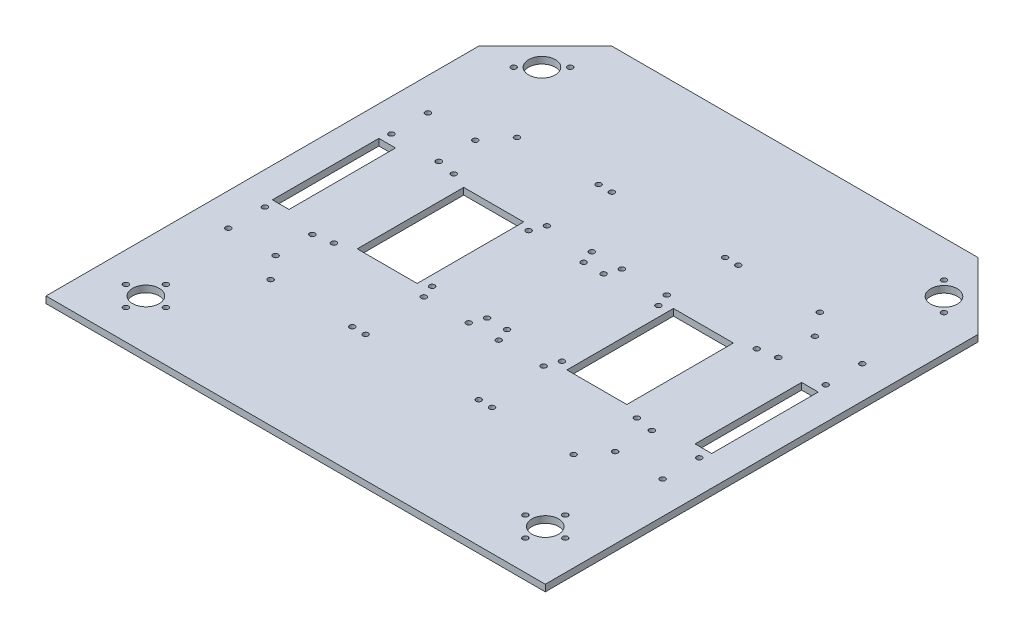
SolidWorks part; units mm, degrees
ref_plane "Plan de face" through (0, 0, 0) normal (0, 0, 1) x (1, 0, 0)
ref_plane "Plan de dessus" through (0, 0, 0) normal (0, 1, 0) x (1, 0, 0)
ref_plane "Plan de droite" through (0, 0, 0) normal (1, 0, 0) x (0, 0, -1)
sketch "Esquisse1" plane through (0, 0, 0) normal (0, 1, 0) x (1, 0, 0)
  line L0 (-150, 0) -> (-150, 260)
  line L2 (150, 0) -> (150, 260)
  line L3 (-150, 260) -> (-110, 260) construction
  line L4 (-110, 260) -> (-110, 300) construction
  line L5 (150, 260) -> (110, 260) construction
  line L6 (110, 260) -> (110, 300) construction
  line L8 (-150, 260) -> (-110, 300)
  line L9 (-110, 300) -> (110, 300)
  line L10 (0, 0) -> (0, 300) construction
  line L11 (110, 300) -> (150, 260)
  line L12 (-150, 0) -> (-119.9849, 0) construction
  line L13 (-119.9849, 0) -> (-119.9849, 30) construction
  line L14 (150, 0) -> (120, 0) construction
  line L15 (120, 0) -> (120, 30) construction
  line L16 (-150, 0) -> (150, 0)
  line L17 (-150, 260) -> (-120, 260) construction
  line L18 (-120, 260) -> (-120, 268) construction
  line L19 (150, 260) -> (120, 260) construction
  line L20 (120, 260) -> (120, 269.5596) construction
  line L21 (-120, 268) -> (-111.5147, 276.4853) construction
  line L22 (-120, 268) -> (-128.4853, 259.5147) construction
  line L23 (120, 269.5596) -> (128.4853, 261.0743) construction
  line L24 (120, 269.5596) -> (111.5147, 278.0449) construction
  line L25 (120, 0) -> (120, 19.3937) construction
  line L26 (120, 30) -> (120, 19.3937) construction
  line L27 (120, 30) -> (120, 42) construction
  line L28 (-119.9849, 0) -> (-119.9849, 18) construction
  line L29 (-119.9849, 18) -> (-119.9849, 30) construction
  line L30 (-119.9849, 30) -> (-119.9849, 42) construction
  line L31 (120, 0) -> (120, 18) construction
  line L32 (150, 150) -> (-150, 150) construction
  line L33 (-119.9849, 30) -> (-107.9849, 30) construction
  line L34 (-119.9849, 30) -> (-131.9849, 30) construction
  line L35 (120, 30) -> (132, 30) construction
  line L36 (120, 30) -> (108, 30) construction
  circle A2 centre (-119.9849, 30) radius 8
  circle A4 centre (-120, 268) radius 8
  circle A5 centre (120, 269.5596) radius 8
  circle A6 centre (-111.5147, 276.4853) radius 1.6
  circle A7 centre (-128.4853, 259.5147) radius 1.6
  circle A8 centre (111.5147, 278.0449) radius 1.6
  circle A9 centre (128.4853, 261.0743) radius 1.6
  circle A10 centre (120, 30) radius 8
  circle A11 centre (120, 42) radius 1.6
  circle A13 centre (-119.9849, 42) radius 1.6
  circle A14 centre (-119.9849, 18) radius 1.6
  circle A15 centre (120, 18) radius 1.6
  circle A16 centre (-131.9849, 30) radius 1.6
  circle A17 centre (-107.9849, 30) radius 1.6
  circle A18 centre (108, 30) radius 1.6
  circle A19 centre (132, 30) radius 1.6
extrude "Boss.-Extru.1" add sketch "Esquisse1" along normal blind 4
sketch "Esquisse3" plane through (0, 4, 0) normal (0, 1, 0) x (1, 0, 0)
  line L0 (-150, 0) -> (150, 0) construction
  line L1 (150, 0) -> (150, 260) construction
  line L2 (150, 260) -> (110, 300) construction
  line L3 (110, 300) -> (-110, 300) construction
  line L4 (-110, 300) -> (-150, 260) construction
  line L5 (-150, 260) -> (-150, 0) construction
  line L6 (-150, 150) -> (150, 150) construction
  line L7 (0, 300) -> (0, 0) construction
  line L8 (0, 150) -> (-5, 150) construction
  line L9 (0, 150) -> (5, 150) construction
  line L10 (-5, 150) -> (-5, 175) construction
  line L11 (-5, 150) -> (-5, 109) construction
  line L12 (-5, 109) -> (-13, 109) construction
  line L13 (-13, 109) -> (-13, 117) construction
  line L14 (-13, 117) -> (-5, 117) construction
  line L15 (-5, 117) -> (-5, 109) construction
  line L16 (-13, 117) -> (-5, 109) construction
  line L17 (-13, 109) -> (-5, 117) construction
  line L18 (-5, 175) -> (-10, 175) construction
  line L19 (-10, 175) -> (-10, 183) construction
  line L20 (-10, 183) -> (-2, 183) construction
  line L23 (-5, 175) -> (-2, 175) construction
  line L24 (-2, 175) -> (-2, 183) construction
  line L25 (-10, 183) -> (-2, 175) construction
  line L26 (-10, 175) -> (-2, 183) construction
  line L27 (-5, 117) -> (-40, 117) construction
  line L28 (-40, 117) -> (-40, 175) construction
  line L29 (-40, 175) -> (-35, 175) construction
  line L30 (-35, 175) -> (-35, 125) construction
  line L31 (-35, 125) -> (-10, 125) construction
  line L32 (-10, 175) -> (-10, 125) construction
  line L33 (-40, 117) -> (-40, 109) construction
  line L34 (-40, 109) -> (-32, 109) construction
  line L35 (-32, 109) -> (-32, 117) construction
  line L36 (-32, 117) -> (-40, 109) construction
  line L37 (-40, 117) -> (-32, 109) construction
  line L38 (-40, 175) -> (-43, 175) construction
  line L39 (-43, 175) -> (-43, 183) construction
  line L40 (-43, 183) -> (-35, 183) construction
  line L41 (-35, 183) -> (-35, 175) construction
  line L42 (-35, 175) -> (-43, 183) construction
  line L43 (-43, 175) -> (-35, 183) construction
  line L44 (5, 125) -> (5, 183) construction
  line L45 (5, 125) -> (10, 125) construction
  line L47 (10, 125) -> (10, 175) construction
  line L50 (5, 183) -> (40, 183) construction
  line L51 (40, 183) -> (40, 125) construction
  line L52 (40, 125) -> (35, 125) construction
  line L53 (35, 125) -> (35, 175) construction
  line L54 (35, 175) -> (10, 175) construction
  line L55 (10, 125) -> (10, 117) construction
  line L56 (10, 117) -> (2, 117) construction
  line L57 (2, 117) -> (2, 125) construction
  line L58 (2, 125) -> (5, 125) construction
  line L59 (35, 125) -> (35, 117) construction
  line L60 (35, 117) -> (43, 117) construction
  line L61 (43, 117) -> (43, 125) construction
  line L62 (43, 125) -> (40, 125) construction
  line L63 (5, 183) -> (5, 191) construction
  line L64 (5, 191) -> (13, 191) construction
  line L65 (13, 191) -> (13, 183) construction
  line L66 (40, 183) -> (40, 191) construction
  line L67 (40, 191) -> (32, 191) construction
  line L68 (32, 191) -> (32, 183) construction
  line L69 (32, 183) -> (40, 191) construction
  line L70 (40, 183) -> (32, 191) construction
  line L71 (5, 191) -> (13, 183) construction
  line L72 (13, 191) -> (5, 183) construction
  line L73 (2, 125) -> (10, 117) construction
  line L74 (2, 117) -> (10, 125) construction
  line L75 (35, 125) -> (43, 117) construction
  line L76 (35, 117) -> (43, 125) construction
  circle A0 centre (-9, 113) radius 1.6
  circle A1 centre (-6, 179) radius 1.6
  circle A2 centre (-39, 179) radius 1.6
  circle A3 centre (-36, 113) radius 1.6
  circle A4 centre (9, 187) radius 1.6
  circle A5 centre (36, 187) radius 1.6
  circle A6 centre (39, 121) radius 1.6
  circle A7 centre (6, 121) radius 1.6
  dimension "D1" = 58
  dimension "D7" = 5
  dimension "D2" = 8
  dimension "D3" = 8
  dimension "D4" = 25
  dimension "D5" = 35
  dimension "D6" = 50
extrude "Enlèv. mat.-Extru.1" cut sketch "Esquisse3" against normal blind 10
sketch "Esquisse4" plane through (0, 4, 0) normal (0, 1, 0) x (1, 0, 0)
  line L0 (0, 150) -> (-45, 150)
  line L1 (0, 0) -> (0, 300) construction
  line L2 (150, 150) -> (-150, 150) construction
  line L3 (-45, 150) -> (-45, 182)
  line L4 (-45, 182) -> (-81, 182)
  line L5 (-81, 182) -> (-81, 118)
  line L6 (-81, 118) -> (-45, 118)
  line L7 (-45, 118) -> (-45, 150)
  line L8 (0, 150) -> (45, 150)
  line L9 (45, 150) -> (45, 182)
  line L10 (45, 182) -> (81, 182)
  line L11 (81, 182) -> (81, 118)
  line L12 (81, 118) -> (45, 118)
  line L13 (45, 118) -> (45, 150)
  dimension "D2" = 64
  dimension "D3" = 36
extrude "Enlèv. mat.-Extru.2" cut sketch "Esquisse4" against normal blind 5 contours L6 L7 L3 L4 L5 | L9 L10 L11 L12 L13 region at (-63, 4, -150)
mirror "Symétrie1" about plane through (0, 0, 0) normal (1, 0, 0) of "Enlèv. mat.-Extru.1"
sketch "Esquisse5" plane through (0, 4, 0) normal (0, 1, 0) x (1, 0, 0)
  line L0 (-150, 260) -> (-110, 300) construction
  line L1 (-110, 300) -> (110, 300) construction
  line L2 (110, 300) -> (150, 260) construction
  line L3 (150, 260) -> (150, 0) construction
  line L4 (150, 0) -> (-150, 0) construction
  line L5 (-150, 0) -> (-150, 260) construction
  line L6 (0, 150) -> (0, 205) construction
  line L7 (0, 0) -> (0, 300) construction
  line L8 (0, 150) -> (0, 95) construction
  line L9 (0, 205) -> (-5, 205) construction
  line L10 (0, 205) -> (-15, 205) construction
  line L11 (-10, 205) -> (-5, 205) construction
  line L13 (-15, 205) -> (-15, 195) construction
  line L14 (-15, 195) -> (-25, 195) construction
  line L16 (-25, 195) -> (-25, 215) construction
  line L17 (-25, 215) -> (-15, 215) construction
  line L18 (-15, 215) -> (-15, 205) construction
  line L19 (-25, 205) -> (-25, 210) construction
  line L20 (-25, 210) -> (-30, 210) construction
  line L21 (-30, 210) -> (-30, 200) construction
  line L22 (-30, 200) -> (-25, 200) construction
  line L23 (0, 205) -> (-30, 205)
  line L24 (-30, 205) -> (-30, 190) construction
  line L29 (-30, 220) -> (-30, 205) construction
  line L30 (-30, 220) -> (-30, 228) construction
  line L31 (-30, 228) -> (-38, 228) construction
  line L32 (-38, 228) -> (-38, 220) construction
  line L33 (-38, 220) -> (-30, 220) construction
  line L34 (-38, 228) -> (-46, 228) construction
  line L35 (-46, 228) -> (-46, 220) construction
  line L37 (-30, 220) -> (-95, 220) construction
  line L38 (-95, 220) -> (-95, 190) construction
  line L39 (-95, 190) -> (-30, 190) construction
  line L40 (95, 80) -> (95, 72) construction
  line L41 (95, 72) -> (87, 72) construction
  line L42 (-46, 228) -> (-38, 220) construction
  line L43 (-38, 220) -> (-30, 228) construction
  line L44 (-46, 220) -> (-38, 228) construction
  line L45 (-38, 228) -> (-30, 220) construction
  line L49 (87, 72) -> (87, 80) construction
  line L50 (87, 80) -> (95, 72) construction
  line L51 (0, 95) -> (30, 95) construction
  line L52 (30, 95) -> (30, 110) construction
  line L56 (30, 80) -> (30, 95) construction
  line L57 (30, 80) -> (30, 72) construction
  line L58 (30, 72) -> (38, 72) construction
  line L59 (38, 72) -> (38, 80) construction
  line L60 (38, 80) -> (30, 80) construction
  line L61 (38, 80) -> (46, 80) construction
  line L62 (46, 80) -> (46, 72) construction
  line L63 (46, 72) -> (38, 72) construction
  line L64 (46, 80) -> (38, 72) construction
  line L65 (30, 80) -> (38, 72) construction
  line L66 (30, 72) -> (38, 80) construction
  line L67 (46, 72) -> (38, 80) construction
  line L72 (30, 110) -> (95, 110) construction
  line L73 (95, 110) -> (95, 80) construction
  line L74 (95, 80) -> (46, 80) construction
  line L78 (95, 72) -> (87, 72) construction
  line L79 (87, 72) -> (95, 80) construction
  line L80 (95, 110) -> (95, 118) construction
  line L81 (95, 88) -> (95, 110) construction
  line L82 (95, 118) -> (87, 118) construction
  line L83 (87, 118) -> (87, 110) construction
  line L84 (87, 110) -> (95, 118) construction
  line L85 (95, 118) -> (87, 118) construction
  line L86 (87, 118) -> (95, 110) construction
  line L87 (-95, 190) -> (-95, 182) construction
  line L88 (95, 110) -> (95, 88) construction
  line L89 (-95, 182) -> (-87, 182) construction
  line L90 (-87, 182) -> (-87, 190) construction
  line L91 (-87, 190) -> (-95, 182) construction
  line L92 (-95, 182) -> (-87, 182) construction
  line L93 (-87, 182) -> (-95, 190) construction
  line L94 (-95, 190) -> (-95, 220) construction
  line L95 (-95, 220) -> (-95, 228) construction
  line L96 (-95, 228) -> (-87, 228) construction
  line L97 (-87, 228) -> (-87, 220) construction
  line L98 (-87, 220) -> (-95, 228) construction
  line L99 (-95, 228) -> (-95, 220) construction
  line L100 (-95, 220) -> (-87, 228) construction
  circle A2 centre (-42, 224) radius 1.6
  circle A3 centre (-34, 224) radius 1.6
  circle A4 centre (34, 76) radius 1.6
  circle A5 centre (42, 76) radius 1.6
  circle A13 centre (91, 114) radius 1.6
  circle A14 centre (91, 76) radius 1.6
  circle A15 centre (-91, 224) radius 1.6
  circle A16 centre (-91, 186) radius 1.6
  dimension "D1" = 30
  dimension "D2" = 55
extrude "Enlèv. mat.-Extru.4" cut sketch "Esquisse5" against normal blind 5 contours A3 | A2 | A13 | A14 | A4 | A5 | A16 | A15 region at (-42, 4, -224) region at (-34, 4, -224) region at (34, 4, -76) region at (42, 4, -76) region at (91, 4, -114) region at (91, 4, -76) region at (-91, 4, -224) region at (-91, 4, -186)
mirror "Symétrie4" about plane through (0, 0, 0) normal (1, 0, 0) of "Enlèv. mat.-Extru.4"
sketch "Esquisse6" plane through (0, 4, 0) normal (0, 1, 0) x (1, 0, 0)
  line L0 (-106, 150) -> (-106, 116) construction
  line L1 (-106, 116) -> (-98, 116) construction
  line L2 (0, 150) -> (-85, 150) construction
  line L3 (-85, 150) -> (-106, 150) construction
  line L4 (-98, 116) -> (-98, 108) construction
  line L5 (-98, 108) -> (-106, 108) construction
  line L6 (-106, 108) -> (-106, 116) construction
  line L8 (-106, 116) -> (-126.5, 116) construction
  line L11 (-106, 116) -> (-106, 86) construction
  line L12 (-126.5, 116) -> (-126.5, 86) construction
  line L13 (-126.5, 86) -> (-106, 86) construction
  line L14 (-106, 86) -> (-98, 86) construction
  line L15 (-98, 86) -> (-98, 94) construction
  line L16 (-98, 94) -> (-106, 94) construction
  line L17 (-106, 94) -> (-98, 86) construction
  line L18 (-106, 116) -> (-98, 108) construction
  line L19 (-106, 116) -> (-106, 108) construction
  line L20 (-106, 108) -> (-98, 116) construction
  line L21 (-126.5, 86) -> (-134.5, 86) construction
  line L22 (-134.5, 86) -> (-134.5, 94) construction
  line L23 (-134.5, 94) -> (-126.5, 94) construction
  line L24 (-126.5, 94) -> (-134.5, 86) construction
  line L25 (-134.5, 86) -> (-134.5, 94) construction
  line L26 (-134.5, 94) -> (-126.5, 86) construction
  line L27 (-98, 86) -> (-98, 94) construction
  line L28 (-98, 94) -> (-106, 86) construction
  line L29 (-106, 86) -> (-126.5, 86) construction
  line L30 (-126.5, 86) -> (-126.5, 116) construction
  line L31 (-126.5, 116) -> (-134.5, 116) construction
  line L32 (-134.5, 116) -> (-134.5, 108) construction
  line L33 (-134.5, 108) -> (-126.5, 108) construction
  line L34 (-126.5, 108) -> (-134.5, 116) construction
  line L35 (-134.5, 116) -> (-134.5, 108) construction
  line L36 (0, 150) -> (85, 150) construction
  line L37 (150, 150) -> (-150, 150) construction
  line L38 (85, 150) -> (106, 150) construction
  line L39 (106, 150) -> (106, 184) construction
  line L40 (106, 184) -> (98, 184) construction
  line L41 (98, 184) -> (98, 192) construction
  line L42 (98, 192) -> (106, 192) construction
  line L43 (106, 192) -> (106, 184) construction
  line L44 (106, 184) -> (98, 192) construction
  line L45 (98, 192) -> (106, 192) construction
  line L46 (106, 192) -> (98, 184) construction
  line L47 (98, 184) -> (106, 184) construction
  line L48 (106, 214) -> (126.5, 214) construction
  line L49 (126.5, 214) -> (126.5, 184) construction
  line L50 (126.5, 184) -> (106, 184) construction
  line L51 (126.5, 184) -> (134.5, 184) construction
  line L52 (134.5, 184) -> (134.5, 192) construction
  line L53 (134.5, 192) -> (126.5, 192) construction
  line L54 (126.5, 192) -> (134.5, 184) construction
  line L55 (106, 214) -> (106, 192) construction
  line L56 (106, 214) -> (98, 214) construction
  line L57 (98, 214) -> (98, 206) construction
  line L58 (98, 206) -> (106, 206) construction
  line L59 (106, 206) -> (98, 214) construction
  line L60 (98, 214) -> (98, 206) construction
  line L61 (98, 206) -> (106, 214) construction
  line L62 (134.5, 184) -> (134.5, 192) construction
  line L63 (134.5, 192) -> (126.5, 184) construction
  line L64 (126.5, 184) -> (126.5, 214) construction
  line L65 (126.5, 214) -> (134.5, 214) construction
  line L66 (134.5, 214) -> (134.5, 206) construction
  line L67 (134.5, 206) -> (126.5, 206) construction
  line L68 (126.5, 206) -> (134.5, 214) construction
  line L69 (134.5, 214) -> (126.5, 214) construction
  line L70 (126.5, 214) -> (134.5, 206) construction
  line L71 (-134.5, 108) -> (-126.5, 116) construction
  circle A4 centre (-102, 112) radius 1.6
  circle A6 centre (-102, 90) radius 1.6
  circle A8 centre (102, 188) radius 1.6219
  circle A11 centre (102, 210) radius 1.6
  circle A12 centre (-130.5, 112) radius 1.6
  circle A13 centre (-130.5, 90) radius 1.6
  circle A14 centre (130.5, 210) radius 1.6
  circle A15 centre (130.5, 188) radius 1.6
  dimension "D3" = 21
  dimension "D1" = 85
  dimension "D2" = 34
extrude "Enlèv. mat.-Extru.5" cut sketch "Esquisse6" against normal blind 5
sketch "Esquisse7" plane through (0, 4, 0) normal (0, 1, 0) x (1, 0, 0)
  line L0 (0, 150) -> (-122, 150) construction
  line L1 (0, 0) -> (0, 300) construction
  line L2 (150, 150) -> (-150, 150) construction
  line L3 (-122, 150) -> (-122, 182)
  line L4 (-122, 182) -> (-132, 182)
  line L5 (-132, 182) -> (-132, 118)
  line L6 (-132, 118) -> (-122, 118)
  line L7 (-122, 118) -> (-122, 150)
extrude "Enlèv. mat.-Extru.6" cut sketch "Esquisse7" against normal blind 5
mirror "Symétrie5" about plane through (0, 0, 0) normal (1, 0, 0) of "Enlèv. mat.-Extru.6"
mirror "Symétrie6" about plane through (0, 0, 0) normal (1, 0, 0) of "Enlèv. mat.-Extru.5"
